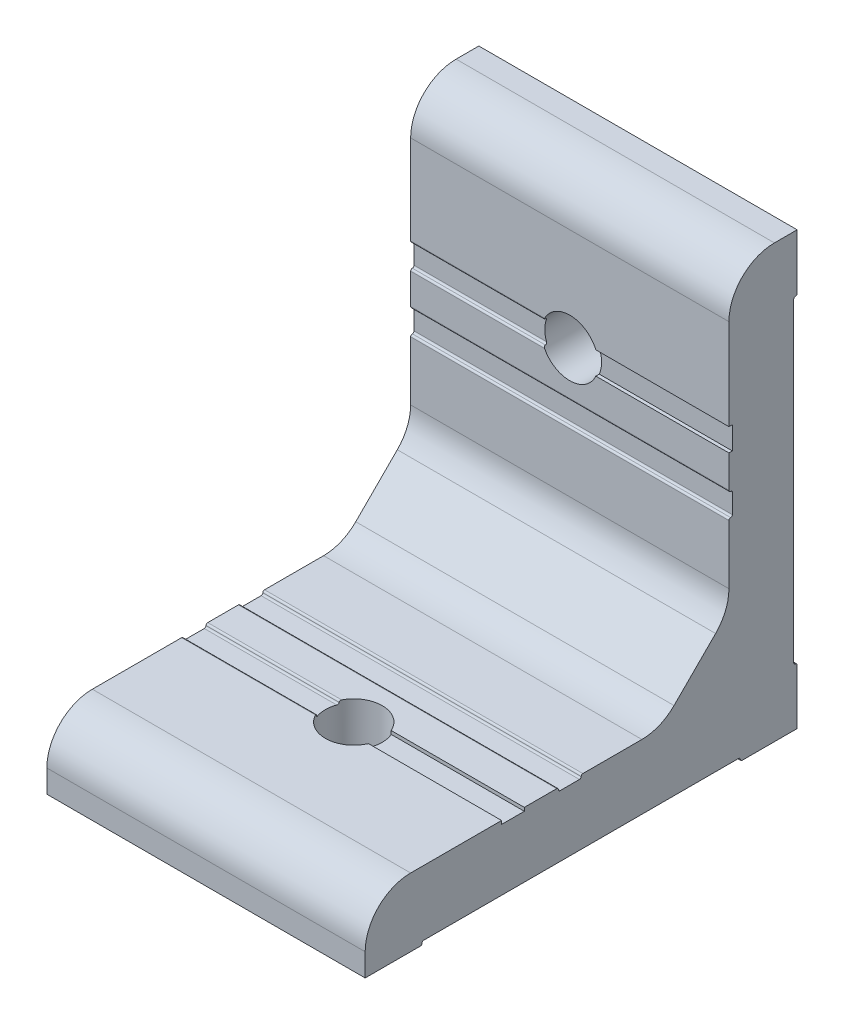
SolidWorks part; units mm, degrees
ref_plane "Plano frontal" through (0, 0, 0) normal (0, 0, 1) x (1, 0, 0)
ref_plane "Plano superior" through (0, 0, 0) normal (0, 1, 0) x (1, 0, 0)
ref_plane "Plano direito" through (0, 0, 0) normal (1, 0, 0) x (0, 0, -1)
ref_plane "Plano1" through (10, 0, 0) normal (1, 0, 0) x (0, 0, -1)
sketch "Esboço1" plane through (10, 0, 0) normal (1, 0, 0) x (0, 0, -1)
  line L0 (7, 38) -> (-31, 38)
  line L1 (-31, 38) -> (-31, 0)
  line L2 (-31, 0) -> (7, 0)
  line L3 (7, 0) -> (7, 38)
  dimension "D1" = 38
extrude "Ressalto-extrusão1" add sketch "Esboço1" against normal blind 28
sketch "Esboço2" plane through (-18, 0, 0) normal (-1, 0, 0) x (0, 0, 1)
  line L0 (31, 38) -> (-1, 38)
  line L1 (-1, 38) -> (-1, 12)
  line L2 (-1, 12) -> (5, 6)
  line L3 (5, 6) -> (31, 6)
  line L4 (31, 6) -> (31, 38)
  line L5 (31, 0) -> (-7, 0) construction
  line L6 (-7, 0) -> (-7, 38) construction
  line L7 (-7, 38) -> (31, 38) construction
  dimension "D1" = 6
  dimension "D2" = 6
  dimension "D3" = 6
  dimension "D4" = 6
extrude "Corte-extrusão1" cut sketch "Esboço2" against normal through all
sketch "Esboço7" plane through (10, 0, 0) normal (1, 0, 0) x (0, 0, -1)
  line L0 (7, 0) -> (7, 38) construction
  line L1 (7, 33) -> (6.7, 33)
  line L2 (7, 33) -> (7, 5)
  line L3 (7, 5) -> (6.7, 5)
  line L4 (6.7, 33) -> (6.7, 5)
  line L5 (-31, 0) -> (7, 0) construction
  line L6 (2, 0) -> (-26, 0)
  line L7 (2, 0) -> (2, 0.3)
  line L8 (2, 0.3) -> (-26, 0.3)
  line L9 (-26, 0) -> (-26, 0.3)
  line L10 (7, 38) -> (1, 38) construction
  line L11 (-31, 6) -> (-31, 0) construction
  line L12 (-5, 6) -> (-31, 6) construction
  line L13 (-14, 6) -> (-12, 6)
  line L14 (-14, 6) -> (-14, 5.7)
  line L15 (-14, 5.7) -> (-12, 5.7)
  line L16 (-12, 6) -> (-12, 5.7)
  line L17 (1, 38) -> (1, 12) construction
  line L18 (1, 21) -> (1.3, 21)
  line L19 (1, 21) -> (1, 19)
  line L20 (1, 19) -> (1.3, 19)
  line L21 (1.3, 21) -> (1.3, 19)
  line L22 (-19, 6) -> (-19, 5.7)
  line L23 (-17, 6) -> (-17, 5.7)
  line L24 (-19, 6) -> (-17, 6)
  line L25 (-19, 5.7) -> (-17, 5.7)
  line L26 (1.3, 26) -> (1.3, 24)
  line L27 (1, 26) -> (1, 24)
  line L28 (1, 26) -> (1.3, 26)
  line L29 (1, 24) -> (1.3, 24)
  point P28 (-13, 5.7)
  point P29 (1.3, 20)
  point P34 (-18, 5.7)
  point P39 (1.3, 25)
  dimension "D1" = 5
  dimension "D2" = 5
  dimension "D3" = 5
  dimension "D4" = 5
  dimension "D5" = 0.3
  dimension "D6" = 0.3
  dimension "D7" = 2
  dimension "D8" = 0.3
  dimension "D9" = 2
  dimension "D10" = 0.3
  dimension "D11" = 20
  dimension "D12" = 20
extrude "Corte-extrusão2" cut sketch "Esboço7" against normal through all
hole_wizard "Furo de diâmetro Ø7.0 (7)3" positions "Esboço4" profile "Esboço3" hole size "Ø7.0" standard "Ansi Metric" end condition through all
sketch "Esboço4" plane through (0, 6, 0) normal (0, 1, 0) x (1, 0, 0)
  line L0 (10, -31) -> (-18, -31) construction
  line L1 (-18, 7) -> (10, 7) construction
  point P0 (-4, -18)
  point P3 (-4, -31)
  dimension "D1" = 25
sketch "Esboço3" plane through (-4, 6, 18) normal (1, 0, 0) x (0, 0, 1)
  line L0 (0, 0) -> (0, 6)
  line L1 (0, 6) -> (2.5, 6)
  line L2 (2.5, 6) -> (2.5, 0)
  line L5 (2.5, 0) -> (0, 0)
  line L11 (0, -6.35) -> (0, 107.95) construction
  dimension "Thru Hole Dia." = 5
  dimension "Thru Hole Depth" = 6
hole_wizard "Furo de diâmetro Ø7.0 (7)2" positions "Esboço6" profile "Esboço5" hole size "Ø7.0" standard "Ansi Metric" end condition through all
sketch "Esboço6" plane through (0, 0, -7) normal (0, 0, -1) x (-1, 0, 0)
  line L0 (18, 38) -> (-10, 38) construction
  line L1 (18, 0) -> (-10, 0) construction
  point P0 (4, 25)
  point P3 (4, 38)
  dimension "D1" = 25
sketch "Esboço5" plane through (-4, 25, -7) normal (1, 0, 0) x (0, 1, 0)
  line L0 (0, 0) -> (0, 38)
  line L1 (0, 38) -> (2.5, 38)
  line L2 (2.5, 38) -> (2.5, 0)
  line L5 (2.5, 0) -> (0, 0)
  line L11 (0, -6.35) -> (0, 107.95) construction
  dimension "Thru Hole Dia." = 5
  dimension "Thru Hole Depth" = 38
fillet "Filete1" radius 4 4 edges at (-4, 6, 31) (-4, 6, 5) (-4, 38, -1) (-4, 12, -1)
fillet "Filete2" radius 0.15 24 edges at (-4, 5, -7) (-4, 5, -6.7) (-4, 33, -7) (-4, 33, -6.7) (-4, 0, 26) (-4, 0.3, 26) (-4, 0.3, -2) (-4, 0, -2) (-4, 19, -1.3) (-4, 19, -1) (-4, 21, -1.3) (-4, 21, -1) (-4, 5.7, 14) (-4, 6, 14) (-4, 5.7, 12) (-4, 6, 12) (-12.1456, 26, -1.3) (-12.1456, 24, -1.3) (-12.1456, 24, -1) (-12.1456, 26, -1) (-12.1456, 5.7, 19) (-12.1456, 5.7, 17) (-12.1456, 6, 17) (-12.1456, 6, 19)
ref_plane "Plano2" [suppressed] through (2.5, 0, 0) normal (-1, 0, 0) x (0, 0, 1)
equation "\"D2@Esboço2\"=\"D1@Esboço2\""
